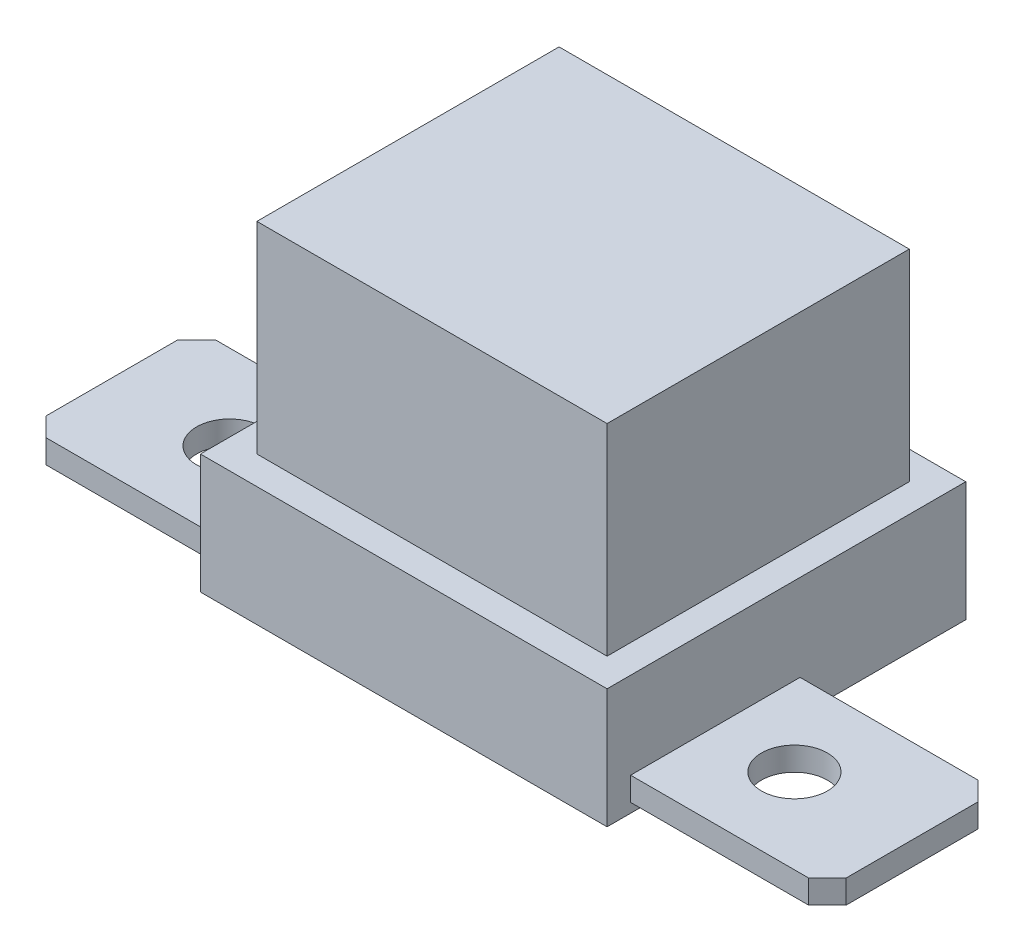
SolidWorks part; units mm, degrees
ref_plane "Front Plane" through (0, 0, 0) normal (0, 0, 1) x (1, 0, 0)
ref_plane "Top Plane" through (0, 0, 0) normal (0, 1, 0) x (1, 0, 0)
ref_plane "Right Plane" through (0, 0, 0) normal (1, 0, 0) x (0, 0, -1)
sketch "Sketch1" plane through (0, 0, 0) normal (0, 1, 0) x (1, 0, 0)
  line L0 (-18.6, -16.05) -> (-18.6, 16.05)
  line L1 (-21.6, -19.05) -> (21.6, -19.05)
  line L2 (-21.6, -19.05) -> (-21.6, 19.05)
  line L3 (-21.6, 19.05) -> (21.6, 19.05)
  line L4 (21.6, -19.05) -> (21.6, 19.05)
  line L5 (-21.6, -19.05) -> (21.6, 19.05) construction
  line L6 (-21.6, 19.05) -> (21.6, -19.05) construction
  line L11 (-18.6, 16.05) -> (18.6, 16.05)
  line L12 (18.6, -16.05) -> (18.6, 16.05)
  line L13 (-18.6, -16.05) -> (18.6, -16.05)
  point P0 (0, 0)
  point P6 (0, 0)
  dimension "D1" = 38.1
  dimension "D2" = 43.2
  dimension "D3" = 3
extrude "Boss-Extrude1" add sketch "Sketch1" along normal blind 34.1 contours L0 L13 L12 L11 region at (0, 0, 0)
extrude "Boss-Extrude2" add sketch "Sketch1<4>" along normal blind 12.7
sketch "Sketch1<4>" plane through (0, 0, 0) normal (0, 1, 0) x (1, 0, 0) same geometry as "Sketch1"
sketch "Sketch2" plane through (0, 0, 0) normal (0, 1, 0) x (1, 0, 0)
  line L0 (-21.6, 19.05) -> (-21.6, -19.05) construction
  line L1 (-21.6, 1.45) -> (-40.5, 1.45)
  line L2 (-21.6, 1.45) -> (-21.6, -16.55)
  line L3 (-21.6, -16.55) -> (-40.5, -16.55)
  line L4 (-42.5, -0.55) -> (-42.5, -14.55)
  line L5 (0, 0) -> (0, 50000) construction
  line L6 (-21.6, -19.05) -> (21.6, -19.05) construction
  line L7 (-40.5, 1.45) -> (-42.5, -0.55)
  line L8 (-40.5, -16.55) -> (-42.5, -14.55)
  line L9 (21.6, -16.55) -> (40.5, -16.55)
  line L10 (40.5, -16.55) -> (42.5, -14.55)
  line L11 (42.5, -0.55) -> (42.5, -14.55)
  line L12 (40.5, 1.45) -> (42.5, -0.55)
  line L13 (21.6, 1.45) -> (40.5, 1.45)
  line L14 (21.6, 1.45) -> (21.6, -16.55)
  circle A0 centre (-30, -7.55) radius 3.5
  circle A1 centre (30, -7.55) radius 3.5
  point P1 (-42.5, -16.55)
  point P3 (-42.5, 1.45)
  point P13 (0, 0)
  point P15 (-27.1027, 1.45)
  dimension "D6" = 7
  dimension "D1" = 20.9
  dimension "D2" = 18
  dimension "D3" = 2.5
  dimension "D4" = 8.4
  dimension "D5" = 11.5
extrude "Boss-Extrude3" add sketch "Sketch2" along normal blind 2.5 from offset 1
